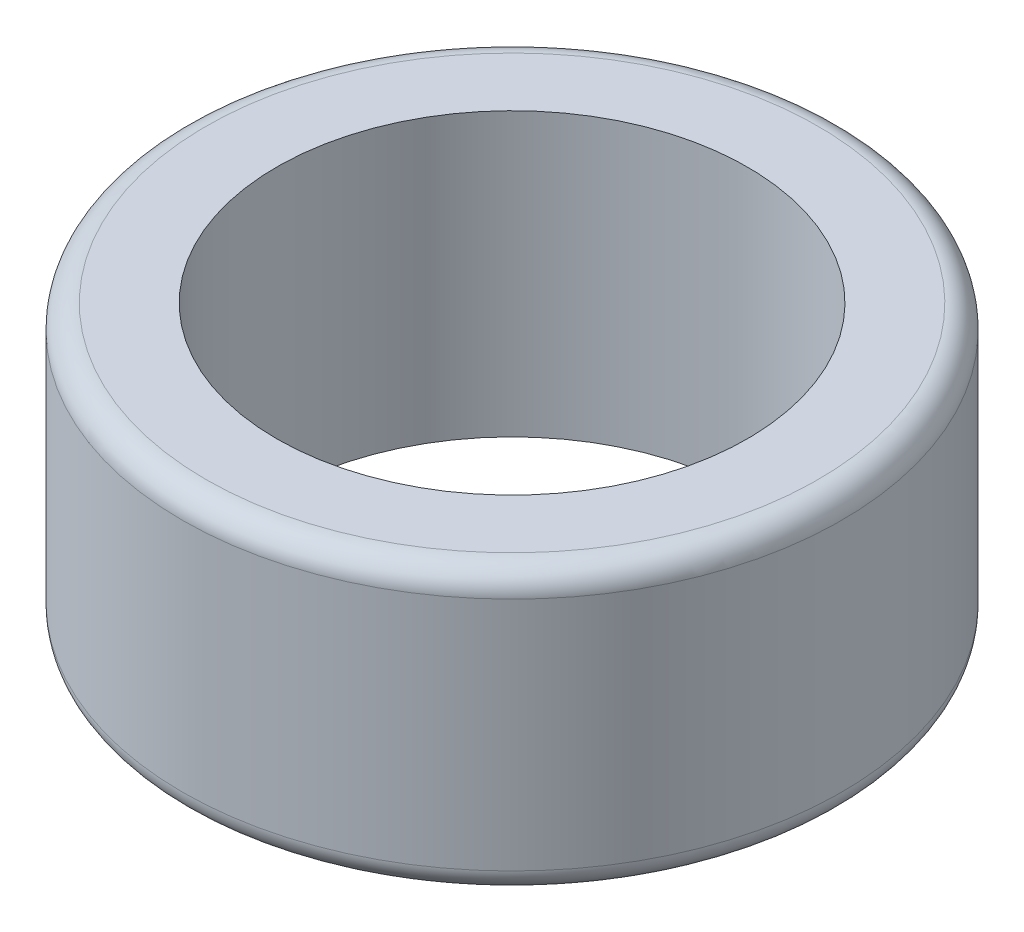
SolidWorks part; units mm, degrees
ref_plane "Front Plane" through (0, 0, 0) normal (0, 0, 1) x (1, 0, 0)
ref_plane "Top Plane" through (0, 0, 0) normal (0, 1, 0) x (1, 0, 0)
ref_plane "Right Plane" through (0, 0, 0) normal (1, 0, 0) x (0, 0, -1)
ref_axis "X-Axis" through (88.99, 0, 0) along (-1, 0, 0)
ref_axis "Y-Axis" through (0, 0, -88.99) along (0, 0, 1)
ref_axis "Z-Axis" through (0, -55, 0) along (0, 1, 0)
sketch "Sketch1" plane through (0, 0, 0) normal (0, 1, 0) x (1, 0, 0)
  circle A0 centre (0, 0) radius 7
  circle A1 centre (0, 0) radius 5
  dimension "D1" = 10
  dimension "D2" = 14
extrude "Boss-Extrude1" add sketch "Sketch1" along normal blind 6
fillet "Fillet1" radius 0.5 2 edges at (0, 0, 7) (0, 6, 7)
